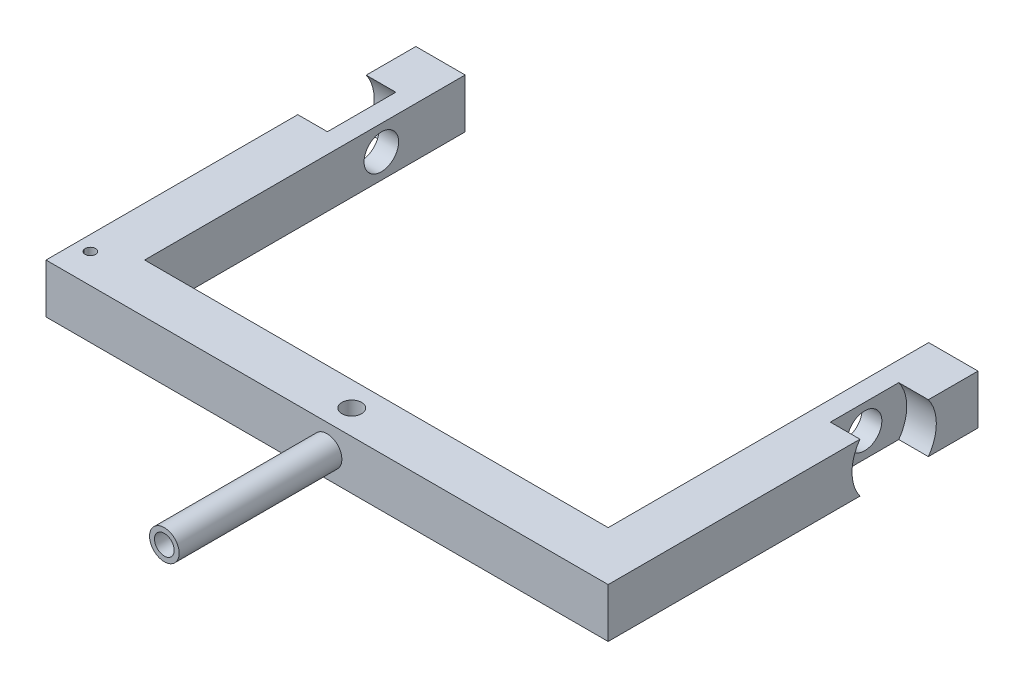
SolidWorks part; units mm, degrees
material "ABS PC"
ref_plane "Front Plane" through (0, 0, 0) normal (0, 0, 1) x (1, 0, 0)
ref_plane "Top Plane" through (0, 0, 0) normal (0, 1, 0) x (1, 0, 0)
ref_plane "Right Plane" through (0, 0, 0) normal (1, 0, 0) x (0, 0, -1)
sketch "Sketch1" plane through (0, 0, 0) normal (0, 1, 0) x (1, 0, 0)
  line L0 (-47, 0) -> (47, 0)
  line L1 (47, 0) -> (47, 65)
  line L2 (47, 65) -> (57, 65)
  line L3 (57, 65) -> (57, -10)
  line L4 (57, -10) -> (-57, -10)
  line L5 (-57, -10) -> (-57, 65)
  line L6 (-57, 65) -> (-47, 65)
  line L7 (-47, 65) -> (-47, 0)
  dimension "D1" = 94
  dimension "D2" = 10
  dimension "D3" = 10
  dimension "D4" = 47
  dimension "D5" = 65
extrude "Boss-Extrude1" add sketch "Sketch1" along normal blind 10
sketch "Sketch2" plane through (57, 0, 0) normal (1, 0, 0) x (0, 0, -1)
  line L0 (65, 10) -> (65, 0) construction
  line L1 (-10, 0) -> (65, 0) construction
  circle A0 centre (48, 5) radius 8.55
  dimension "D1" = 17.1
  dimension "D2" = 17
  dimension "D3" = 5
extrude "Cut-Extrude1" cut sketch "Sketch2" against normal blind 6
mirror "Mirror1" about plane through (0, 0, 0) normal (1, 0, 0) of "Cut-Extrude1"
sketch "Sketch3" plane through (51, 0, 0) normal (1, 0, 0) x (0, 0, -1)
  line L0 (41.0644, 0) -> (54.9356, 0) construction
  line L1 (65, 10) -> (65, 0) construction
  circle A0 centre (48, 5) radius 3.5
  dimension "D1" = 7
  dimension "D2" = 5
  dimension "D3" = 17
extrude "Cut-Extrude2" cut sketch "Sketch3" against normal through all
sketch "Sketch4" plane through (0, 0, 10) normal (0, 0, 1) x (1, 0, 0)
  line L0 (-57, 0) -> (57, 0) construction
  circle A0 centre (0, 5) radius 3
  dimension "D1" = 6
  dimension "D2" = 5
extrude "Boss-Extrude2" add sketch "Sketch4" along normal blind 33
sketch "Sketch5" plane through (0, 10, 0) normal (0, 1, 0) x (1, 0, 0)
  line L2 (-57, 41.0644) -> (-57, -10) construction
  line L3 (-57, -10) -> (57, -10) construction
  circle A0 centre (-54, -4) radius 1.05
  dimension "D2" = 2.1
  dimension "D1" = 3
  dimension "D3" = 6
extrude "Cut-Extrude3" cut sketch "Sketch5" against normal through all
sketch "Sketch6" plane through (0, 0, 43) normal (0, 0, 1) x (1, 0, 0)
  circle A0 centre (0, 5) radius 2
  dimension "D1" = 4
extrude "Cut-Extrude4" cut sketch "Sketch6" against normal blind 38
sketch "Sketch7" plane through (0, 10, 0) normal (0, 1, 0) x (1, 0, 0)
  line L0 (47, 0) -> (-47, 0) construction
  circle A0 centre (0, -5) radius 2
  point P4 (0, 0)
  dimension "D1" = 4
  dimension "D2" = 5
extrude "Cut-Extrude5" cut sketch "Sketch7" against normal blind 5
fillet "Fillet2" radius 6 1 edges at (0, 5, 5)
